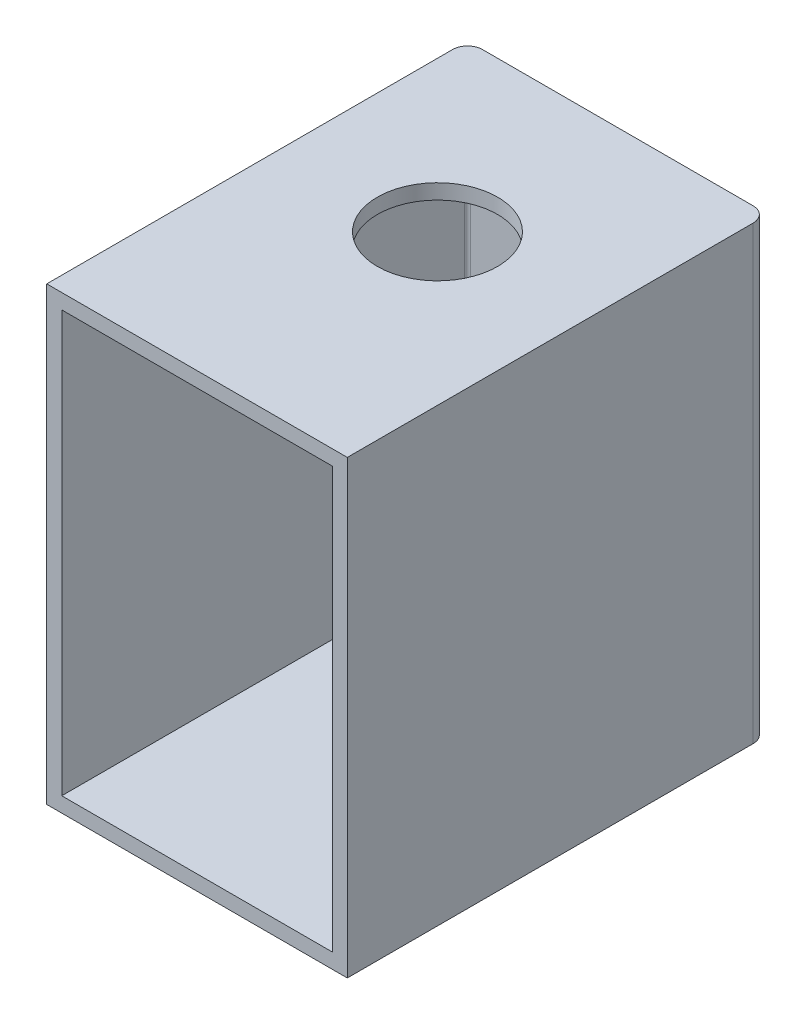
SolidWorks part; units mm, degrees
material "Alloy Steel"
ref_plane "Front Plane" through (0, 0, 0) normal (0, 0, 1) x (1, 0, 0)
ref_plane "Top Plane" through (0, 0, 0) normal (0, 1, 0) x (1, 0, 0)
ref_plane "Right Plane" through (0, 0, 0) normal (1, 0, 0) x (0, 0, -1)
sketch "MainBodyS" plane through (0, 0, 0) normal (0, 1, 0) x (1, 0, 0)
  line L1 (-10, 14) -> (10, 14)
  line L2 (-10, 14) -> (-10, -14)
  line L3 (-10, -14) -> (10, -14)
  line L4 (10, 14) -> (10, -14)
  line L5 (-10, 14) -> (10, -14) construction
  line L6 (-10, -14) -> (10, 14) construction
  point P0 (0, 0)
  dimension "Width" = 20
  dimension "Length" = 28
extrude "MAIN BODY" add sketch "MainBodyS" along normal mid plane 30
fillet "MB FILLET" radius 1 2 edges at (-10, 0, -14) (10, 0, -14)
shell "SHELL MB" thickness 1 removed face at (0, 0, 14)
sketch "TopBoreS" plane through (0, 15, 0) normal (0, 1, 0) x (1, 0, 0)
  line L0 (0, 0) -> (0, 2) construction
  line L1 (9, 14) -> (-9, 14) construction
  circle A0 centre (0, 2) radius 4
  dimension "Dia" = 8
  dimension "YLoc" = 12
extrude "TOP BORE" cut sketch "TopBoreS" against normal up to next
sketch "BottomBoreS" plane through (0, -14, 0) normal (0, 1, 0) x (1, 0, 0)
  circle A0 centre (0, 2) radius 4.5
  circle A1 centre (0, 2) radius 4 construction
  dimension "BottomDiaControl" = 0.5
extrude "BOTTOM BORE" cut sketch "BottomBoreS" against normal through all
fillet "MB INNER FILLET" radius 0.2 2 edges at (9, 0, -13) (-9, 0, -13)
